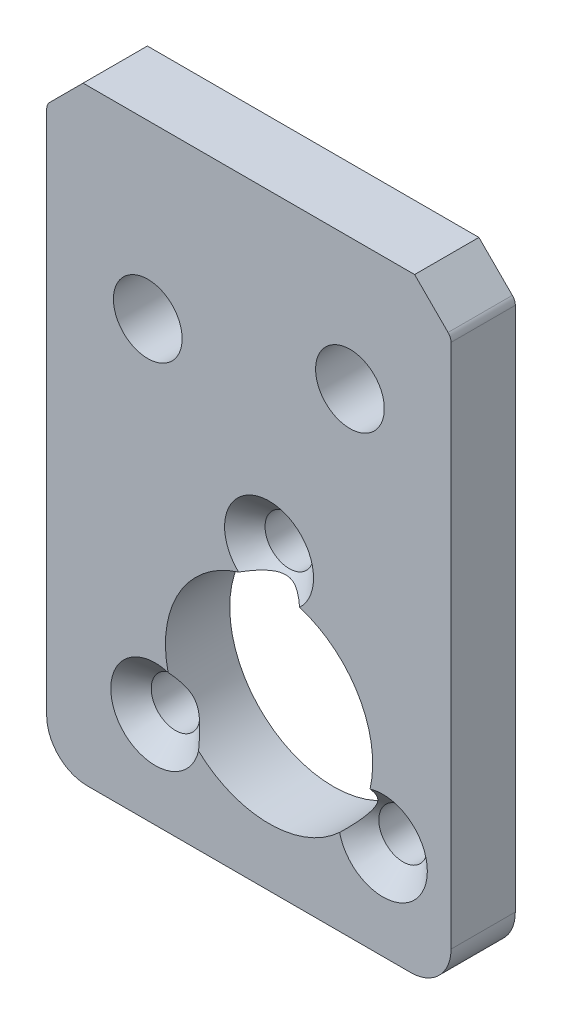
SolidWorks part; units mm, degrees
ref_plane "Front Plane" through (0, 0, 0) normal (0, 0, 1) x (1, 0, 0)
ref_plane "Top Plane" through (0, 0, 0) normal (0, 1, 0) x (1, 0, 0)
ref_plane "Right Plane" through (0, 0, 0) normal (1, 0, 0) x (0, 0, -1)
sketch "Sketch12" plane through (0, 0, 0) normal (0, 0, 1) x (1, 0, 0)
  line L0 (-20, -30) -> (0, -30)
  line L1 (-20, -30) -> (-20, 0)
  line L2 (0, -30) -> (0, 0)
  line L3 (-20, 0) -> (0, 0)
  line L4 (-9, -15.5) -> (-14.6292, -25.25) construction
  line L5 (-14.6292, -25.25) -> (-3.3708, -25.25) construction
  line L6 (-3.3708, -25.25) -> (-9, -15.5) construction
  circle A0 centre (-9, -22) radius 6.5 construction
  circle A6 centre (-9, -22) radius 5.125
  circle A7 centre (-5, -6.5) radius 1.7
  circle A8 centre (-15, -8.5) radius 1.7
  point P8 (-3.3708, -25.25)
  point P11 (-14.6292, -25.25)
  point P13 (-9, -15.5)
  dimension "D1" = 3.4
  dimension "D8" = 10.25
  dimension "D9" = 13
  dimension "D2" = 30
  dimension "D3" = 6.5
  dimension "D4" = 8.5
  dimension "D5" = 5
  dimension "D6" = 15
  dimension "D7" = 22
  dimension "D10" = 9
  dimension "D11" = 20
extrude "Boss-Extrude3" add sketch "Sketch12" along normal blind 3.18
hole_wizard "CSK for M2 Flat Head Machine Screw2" positions "Sketch13" profile "Sketch15" countersink size "M2" standard "ANSI Metric" end condition through all
sketch "Sketch13" plane through (0, 0, 3.18) normal (0, 0, 1) x (1, 0, 0)
  point P0 (-9, -15.5)
  point P3 (-14.6292, -25.25)
  point P6 (-3.3708, -25.25)
sketch "Sketch15" plane through (-9, -15.5, 3.18) normal (1, 0, 0) x (0, -1, 0)
  line L0 (0, 0) -> (0, 3.18)
  line L1 (0, 3.18) -> (1.2, 3.18)
  line L2 (1.2, 3.18) -> (1.2, 1)
  line L3 (1.2, 1) -> (2.2, 0)
  line L5 (2.2, 0) -> (0, 0)
  line L6 (-1.2, 1) -> (-2.2, 0) construction
  line L11 (0, -6.35) -> (0, 107.95) construction
  dimension "Thru Hole Dia." = 2.4
  dimension "Thru Hole Depth" = 3.18
  dimension "Near C'Sink Dia." = 4.4
  dimension "Near C'Sink Angle" = 90
chamfer "Chamfer1" distance 1.8 angle 45 2 edges at (-20, 0, 1.59) (0, 0, 1.59)
fillet "Fillet3" radius 0.5 2 edges at (-20, -1.8, 1.59) (0, -1.8, 1.59)
fillet "Fillet4" radius 2 2 edges at (-20, -30, 1.59) (0, -30, 1.59)
